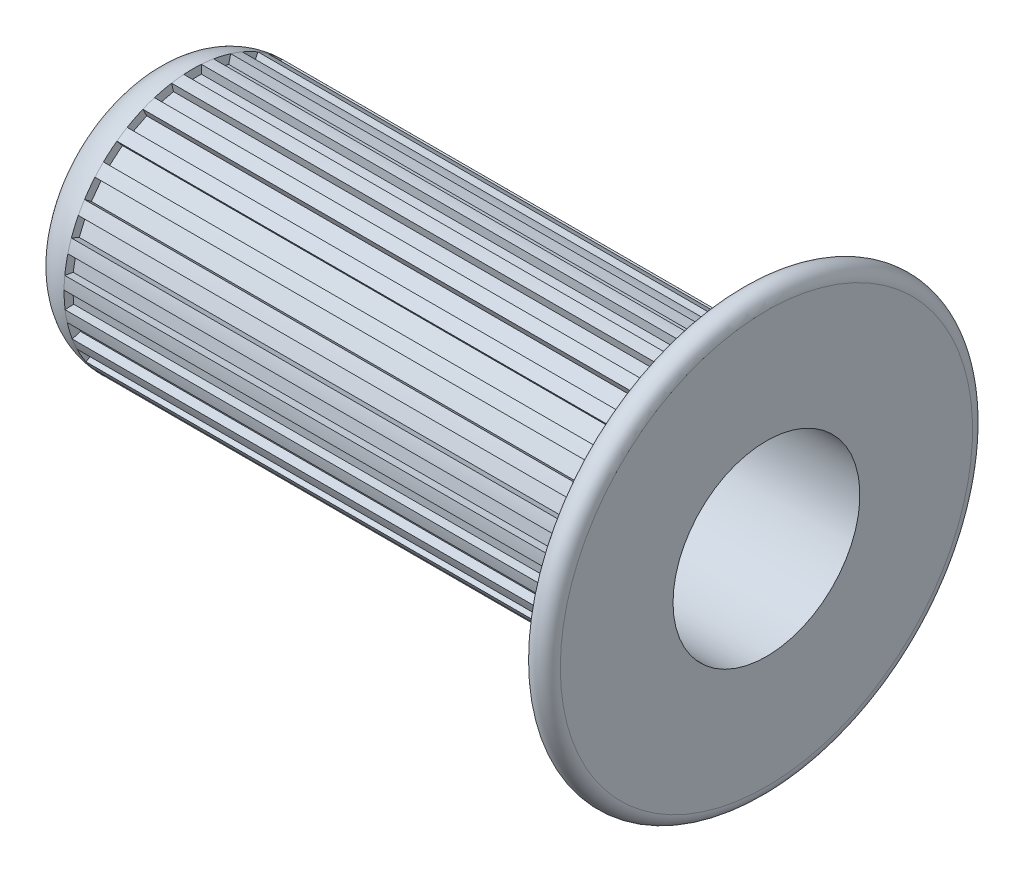
SolidWorks part; units mm, degrees
ref_plane "Front Plane" through (0, 0, 0) normal (0, 0, 1) x (1, 0, 0)
ref_plane "Top Plane" through (0, 0, 0) normal (0, 1, 0) x (1, 0, 0)
ref_plane "Right Plane" through (0, 0, 0) normal (1, 0, 0) x (0, 0, -1)
sketch "Sketch2" plane through (0, 0, 0) normal (0, 0, 1) x (1, 0, 0)
  line L0 (0, 25) -> (0, 10.65)
  line L1 (0, 10.65) -> (-67.42, 10.65)
  line L2 (-67.42, 10.65) -> (-67.42, 0)
  line L3 (-67.42, 0) -> (-70.42, 0)
  line L4 (-70.42, 0) -> (-70.42, 9.65)
  line L5 (-65.42, 14.65) -> (-3, 14.65)
  line L6 (-3, 14.65) -> (-3, 25)
  line L7 (-3, 25) -> (0, 25)
  line L8 (-556.8962, 0) -> (27287.9131, 0) construction
  arc A0 (-70.42, 9.65) -> (-65.42, 14.65) centre (-65.42, 9.65) cw
  dimension "D7" = 5
  dimension "D1" = 67.42
  dimension "D2" = 10.65
  dimension "D3" = 4
  dimension "D4" = 3
  dimension "D5" = 3
  dimension "D6" = 25
revolve "Revolve1" add sketch "Sketch2" angle 360 about L8
fillet "Fillet1" 2 edges at (0, 0, 25) (-3, 0, 25) type full round first side face at (0, 0, 25) second side face at (-3, 0, 14.65) middle face at (-3, 0, 25)
sketch "Sketch3" plane through (-3, 0, 0) normal (-1, 0, 0) x (0, 0, 1)
  line L0 (2.6341, 15.4505) -> (2.1729, 13.5044)
  line L1 (1, 15.6415) -> (-1, 15.6415)
  line L2 (1, 15.6415) -> (1, 13.6415)
  line L3 (1, 13.6415) -> (-1, 13.6415)
  line L4 (-1, 15.6415) -> (-1, 13.6415)
  line L5 (4.5802, 14.9892) -> (2.6341, 15.4505)
  line L6 (4.5802, 14.9892) -> (4.119, 13.0431)
  line L7 (4.119, 13.0431) -> (2.1729, 13.5044)
  line L8 (6.1262, 14.4265) -> (5.2286, 12.6393)
  line L9 (7.9135, 13.5289) -> (6.1262, 14.4265)
  line L10 (7.9135, 13.5289) -> (7.0159, 11.7417)
  line L11 (7.0159, 11.7417) -> (5.2286, 12.6393)
  line L12 (9.2881, 12.6248) -> (8.0025, 11.0928)
  line L13 (10.8202, 11.3393) -> (9.2881, 12.6248)
  line L14 (10.8202, 11.3393) -> (9.5346, 9.8072)
  line L15 (9.5346, 9.8072) -> (8.0025, 11.0928)
  line L16 (11.9492, 10.1426) -> (10.345, 8.9482)
  line L17 (13.1435, 8.5383) -> (11.9492, 10.1426)
  line L18 (13.1435, 8.5383) -> (11.5393, 7.344)
  line L19 (11.5393, 7.344) -> (10.345, 8.9482)
  line L20 (13.9662, 7.1135) -> (12.1297, 6.3213)
  line L21 (14.7583, 5.2771) -> (13.9662, 7.1135)
  line L22 (14.7583, 5.2771) -> (12.9219, 4.4849)
  line L23 (12.9219, 4.4849) -> (12.1297, 6.3213)
  line L24 (15.2302, 3.7009) -> (13.2606, 3.3536)
  line L25 (15.5775, 1.7313) -> (15.2302, 3.7009)
  line L26 (15.5775, 1.7313) -> (13.6079, 1.384)
  line L27 (13.6079, 1.384) -> (13.2606, 3.3536)
  line L28 (15.6731, 0.0888) -> (13.6765, 0.2051)
  line L29 (15.5569, -1.9078) -> (15.6731, 0.0888)
  line L30 (15.5569, -1.9078) -> (13.5602, -1.7915)
  line L31 (13.5602, -1.7915) -> (13.6765, 0.2051)
  line L32 (15.2712, -3.528) -> (13.3552, -2.9544)
  line L33 (14.6976, -5.444) -> (15.2712, -3.528)
  line L34 (14.6976, -5.444) -> (12.7816, -4.8704)
  line L35 (12.7816, -4.8704) -> (13.3552, -2.9544)
  line L36 (14.0459, -6.9547) -> (12.3139, -5.9547)
  line L37 (13.0459, -8.6868) -> (14.0459, -6.9547)
  line L38 (13.0459, -8.6868) -> (11.3139, -7.6868)
  line L39 (11.3139, -7.6868) -> (12.3139, -5.9547)
  line L40 (12.0634, -10.0065) -> (10.6087, -8.634)
  line L41 (10.6909, -11.4612) -> (12.0634, -10.0065)
  line L42 (10.6909, -11.4612) -> (9.2362, -10.0887)
  line L43 (9.2362, -10.0887) -> (10.6087, -8.634)
  line L44 (9.4306, -12.5187) -> (8.3316, -10.8478)
  line L45 (7.7596, -13.6178) -> (9.4306, -12.5187)
  line L46 (7.7596, -13.6178) -> (6.6606, -11.9468)
  line L47 (6.6606, -11.9468) -> (8.3316, -10.8478)
  line L48 (6.2894, -14.3561) -> (5.6053, -12.4768)
  line L49 (4.41, -15.0402) -> (6.2894, -14.3561)
  line L50 (4.41, -15.0402) -> (3.726, -13.1608)
  line L51 (3.726, -13.1608) -> (5.6053, -12.4768)
  line L52 (2.8091, -15.4196) -> (2.5769, -13.4331)
  line L53 (0.8226, -15.6518) -> (2.8091, -15.4196)
  line L54 (0.8226, -15.6518) -> (0.5904, -13.6653)
  line L55 (0.5904, -13.6653) -> (2.5769, -13.4331)
  line L56 (-0.8226, -15.6518) -> (-0.5904, -13.6653)
  line L57 (-2.8091, -15.4196) -> (-0.8226, -15.6518)
  line L58 (-2.8091, -15.4196) -> (-2.5769, -13.4331)
  line L59 (-2.5769, -13.4331) -> (-0.5904, -13.6653)
  line L60 (-4.41, -15.0402) -> (-3.726, -13.1608)
  line L61 (-6.2894, -14.3561) -> (-4.41, -15.0402)
  line L62 (-6.2894, -14.3561) -> (-5.6053, -12.4768)
  line L63 (-5.6053, -12.4768) -> (-3.726, -13.1608)
  line L64 (-7.7596, -13.6178) -> (-6.6606, -11.9468)
  line L65 (-9.4306, -12.5187) -> (-7.7596, -13.6178)
  line L66 (-9.4306, -12.5187) -> (-8.3316, -10.8478)
  line L67 (-8.3316, -10.8478) -> (-6.6606, -11.9468)
  line L68 (-10.6909, -11.4612) -> (-9.2362, -10.0887)
  line L69 (-12.0634, -10.0065) -> (-10.6909, -11.4612)
  line L70 (-12.0634, -10.0065) -> (-10.6087, -8.634)
  line L71 (-10.6087, -8.634) -> (-9.2362, -10.0887)
  line L72 (-13.0459, -8.6868) -> (-11.3139, -7.6868)
  line L73 (-14.0459, -6.9547) -> (-13.0459, -8.6868)
  line L74 (-14.0459, -6.9547) -> (-12.3139, -5.9547)
  line L75 (-12.3139, -5.9547) -> (-11.3139, -7.6868)
  line L76 (-14.6976, -5.444) -> (-12.7816, -4.8704)
  line L77 (-15.2712, -3.528) -> (-14.6976, -5.444)
  line L78 (-15.2712, -3.528) -> (-13.3552, -2.9544)
  line L79 (-13.3552, -2.9544) -> (-12.7816, -4.8704)
  line L80 (-15.5569, -1.9078) -> (-13.5602, -1.7915)
  line L81 (-15.6731, 0.0888) -> (-15.5569, -1.9078)
  line L82 (-15.6731, 0.0888) -> (-13.6765, 0.2051)
  line L83 (-13.6765, 0.2051) -> (-13.5602, -1.7915)
  line L84 (-15.5775, 1.7313) -> (-13.6079, 1.384)
  line L85 (-15.2302, 3.7009) -> (-15.5775, 1.7313)
  line L86 (-15.2302, 3.7009) -> (-13.2606, 3.3536)
  line L87 (-13.2606, 3.3536) -> (-13.6079, 1.384)
  line L88 (-14.7583, 5.2771) -> (-12.9219, 4.4849)
  line L89 (-13.9662, 7.1135) -> (-14.7583, 5.2771)
  line L90 (-13.9662, 7.1135) -> (-12.1297, 6.3213)
  line L91 (-12.1297, 6.3213) -> (-12.9219, 4.4849)
  line L92 (-13.1435, 8.5383) -> (-11.5393, 7.344)
  line L93 (-11.9492, 10.1426) -> (-13.1435, 8.5383)
  line L94 (-11.9492, 10.1426) -> (-10.345, 8.9482)
  line L95 (-10.345, 8.9482) -> (-11.5393, 7.344)
  line L96 (-10.8202, 11.3393) -> (-9.5346, 9.8072)
  line L97 (-9.2881, 12.6248) -> (-10.8202, 11.3393)
  line L98 (-9.2881, 12.6248) -> (-8.0025, 11.0928)
  line L99 (-8.0025, 11.0928) -> (-9.5346, 9.8072)
  line L100 (-7.9135, 13.5289) -> (-7.0159, 11.7417)
  line L101 (-6.1262, 14.4265) -> (-7.9135, 13.5289)
  line L102 (-6.1262, 14.4265) -> (-5.2286, 12.6393)
  line L103 (-5.2286, 12.6393) -> (-7.0159, 11.7417)
  line L104 (-4.5802, 14.9892) -> (-4.119, 13.0431)
  line L105 (-2.6341, 15.4505) -> (-4.5802, 14.9892)
  line L106 (-2.6341, 15.4505) -> (-2.1729, 13.5044)
  line L107 (-2.1729, 13.5044) -> (-4.119, 13.0431)
  circle A0 centre (0, 0) radius 14.65 construction
  point P7 (0, 13.6415)
  point P115 (0, 0)
  dimension "D1" = 2
  dimension "D2" = 2
  dimension "D3" = 15.6415
  dimension "D4" = 27
extrude "Cut-Extrude1" cut sketch "Sketch3" along normal blind 62.42
